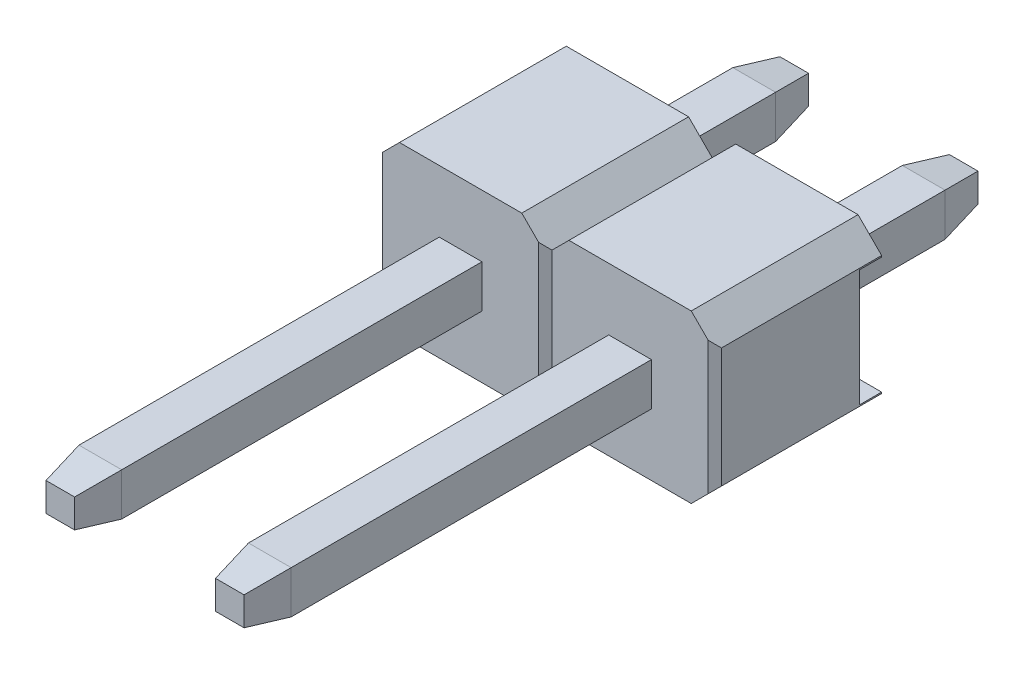
SolidWorks part; units mm, degrees
ref_plane "Front Plane" through (0, 0, 0) normal (0, 0, 1) x (1, 0, 0)
ref_plane "Top Plane" through (0, 0, 0) normal (0, 1, 0) x (1, 0, 0)
ref_plane "Right Plane" through (0, 0, 0) normal (1, 0, 0) x (0, 0, -1)
sketch "Sketch1" plane through (0, 0, 0) normal (0, 0, 1) x (1, 0, 0)
  line L0 (-1.27, 0.8964) -> (-0.9164, 1.25)
  line L1 (-0.9164, 1.25) -> (0.9164, 1.25)
  line L2 (-1.27, 0.8964) -> (-1.27, -0.8964)
  line L3 (-0.9164, -1.25) -> (0.9164, -1.25)
  line L4 (1.27, 0.8964) -> (1.27, -0.8964)
  line L5 (-1.27, -0.8964) -> (-0.9164, -1.25)
  line L6 (0.9164, -1.25) -> (1.27, -0.8964)
  line L7 (1.27, 0.8964) -> (0.9164, 1.25)
  point P0 (1.27, -1.25)
  point P7 (-1.27, 1.25)
  point P10 (-1.27, -1.25)
  point P15 (1.27, 1.25)
  dimension "D5" = 0.25
  dimension "D1" = 2.54
  dimension "D2" = 2.5
  dimension "D3" = 1.27
  dimension "D4" = 1.25
  dimension "D6" = 0.25
  dimension "D7" = 0.25
  dimension "D8" = 0.25
extrude "Extrude1" add sketch "Sketch1" along normal blind 1.25 and the other way blind 1.25
sketch "Sketch4" plane through (0, 0, 0) normal (0, 1, 0) x (1, 0, 0)
  line L0 (-1.27, -1.15) -> (-1.17, -1.25)
  line L1 (-1.17, -1.25) -> (-1.27, -1.25)
  line L2 (-1.27, -1.25) -> (-1.27, -1.15)
  line L3 (1.17, -1.25) -> (1.27, -1.15)
  line L4 (1.27, -1.15) -> (1.27, -1.25)
  line L5 (1.27, -1.25) -> (1.17, -1.25)
extrude "Cut-Extrude3" cut sketch "Sketch4" against normal through all and the other way through all
pattern_linear "LPattern4" count 2 spacing 2.54 along (-1, 0, 0) of "Extrude1", "Cut-Extrude3"
sketch "Sketch2" plane through (0, 0, 0) normal (1, 0, 0) x (0, -1, 0)
  line L1 (-0.8764, 1.25) -> (0.8764, 1.25)
  line L2 (-0.8764, 1.25) -> (-0.8764, 0.92)
  line L3 (-0.8764, 0.92) -> (0.8764, 0.92)
  line L4 (0.8764, 1.25) -> (0.8764, 0.92)
  dimension "D1" = 0.33
extrude "Cut-Extrude1" cut sketch "Sketch2" against normal through all and the other way through all
sketch "Sketch3" plane through (0, 0, 0) normal (1, 0, 0) x (0, 0, -1)
  line L0 (-7.25, 0) -> (3.75, 0)
  line L1 (1.25, 1.25) -> (1.25, 0.8964) construction
  dimension "D1" = 6
  dimension "D2" = 2.5
extrude "Extrude-Thin1" add sketch "Sketch3" along normal blind 0.32 and the other way blind 0.32 thin thin type mid plane wall 0.64
chamfer "Chamfer2" distance 0.6 angle 10 8 edges at (0.32, 0, 7.25) (0, -0.32, 7.25) (-0.32, 0, 7.25) (0, 0.32, 7.25) (0.32, 0, -3.75) (-0.32, 0, -3.75) (0, 0.32, -3.75) (0, -0.32, -3.75) first distance on face at (0.32, 0, 4.25) first distance on face at (0, -0.32, 4.25) first distance on face at (-0.32, 0, 4.25) first distance on face at (0, 0.32, 4.25) first distance on face at (0.32, 0, -2.335) first distance on face at (-0.32, 0, -2.335) first distance on face at (0, 0.32, -2.335) first distance on face at (0, -0.32, -2.335)
pattern_linear "LPattern5" count 1 spacing 2.54 along (1, 0, 0) count 2 spacing 2.54 along (-1, 0, 0) of "Extrude-Thin1", "Chamfer2"
ref_plane "Board Plane" through (0, 0, -1.5) normal (0, 0, 1) x (1, 0, 0)
sketch "Sketch5" plane through (0, 0, 7.25) normal (0, 0, 1) x (1, 0, 0)
  line L0 (-2.54, 0.2142) -> (-2.54, -0.2142) construction
  point P6 (-2.54, 0)
sketch "Sketch6" plane through (0, 0, 7.25) normal (0, 0, 1) x (1, 0, 0)
  point P0 (0, 0)
ref_axis "Axis1" through (0, 0, -3.8748) along (0, 0, 1)
sketch "Sketch7" plane through (0, 0, -3.75) normal (0, 0, -1) x (-1, 0, 0)
  line L0 (2.7542, 0.2142) -> (2.3258, -0.2142) construction
  point P4 (2.54, 0)
ref_axis "Axis2" through (-2.54, 0, 5.1047) along (0, 0, -1)
